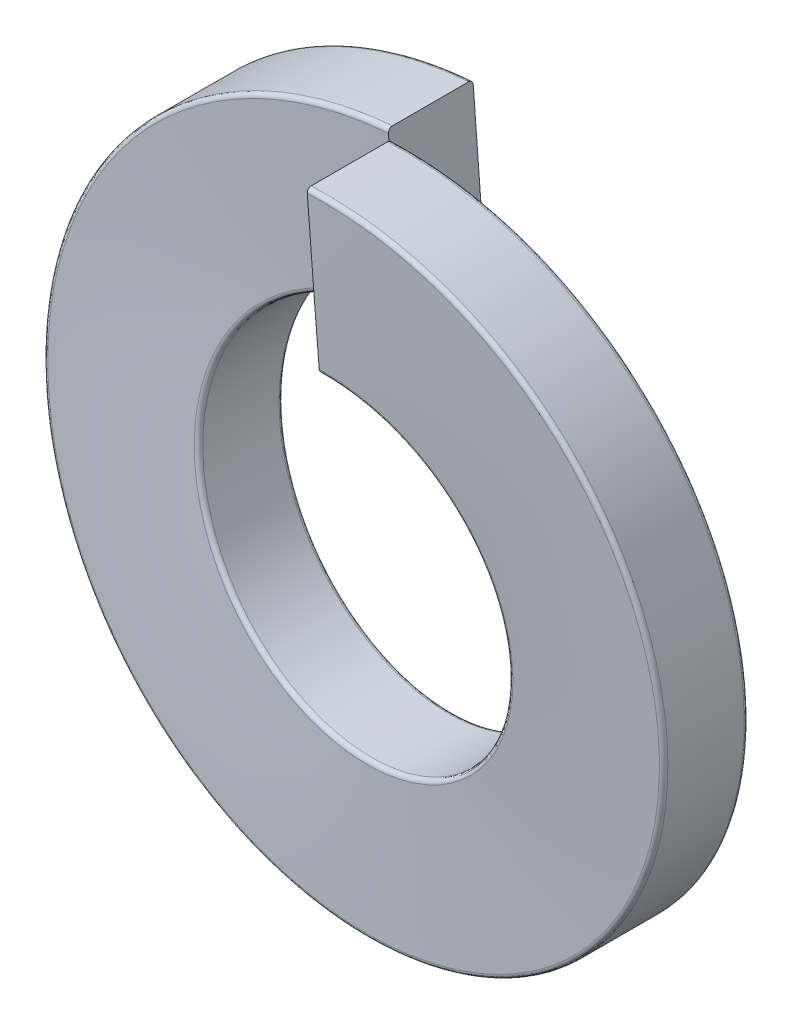
SolidWorks part; units mm, degrees
note: '?' marks a value the reader was unsure of.
material "AISI 316 Stainless Steel Sheet (SS)"
ref_plane "Front Plane" through (0, 0, 0) normal (0, 0, 1) x (1, 0, 0)
ref_plane "Top Plane" through (0, 0, 0) normal (0, 1, 0) x (1, 0, 0)
ref_plane "Right Plane" through (0, 0, 0) normal (1, 0, 0) x (0, 0, -1)
sketch "Sketch1" plane through (0, 0, 0) normal (0, 0, 1) x (1, 0, 0)
  circle A0 centre (0, 0) radius 3.302
  circle A1 centre (0, 0) radius 6.1849
  dimension "OD" = 12.3698
  dimension "ID" = 6.604
sketch "Sketch2" plane through (0, 0, 0) normal (1, 0, 0) x (0, 0, -1)
  line L0 (0, 0) -> (0, 6.1849) construction
  line L1 (0, 6.1849) -> (0, -6.1849) construction
  line L4 (0.1575, 6.1849) -> (1.7323, 6.1849)
  line L5 (1.7323, 6.1849) -> (1.7323, 3.302)
  line L6 (1.7323, 3.302) -> (0.1575, 3.302)
  line L7 (0.1575, 3.302) -> (0.1575, 6.1849)
  point P6 (0, 3.302)
  point P14 (0, -6.1849)
  dimension "Thickness" = 1.5748
  dimension "D1" = 0.1575
ref_plane "Plane1" through (0, 0, -1.7323) normal (0, 0, 1) x (1, 0, 0)
sketch "Sketch3" plane through (0, 0, -1.7323) normal (0, 0, 1) x (1, 0, 0)
  circle A0 centre (0, 0) radius 6.1849 construction
  circle A1 centre (0, 0) radius 6.1849
curve "Helix/Spiral1" pitch 1.7323 height 1.7323 turns 1
sketch "Sketch4" plane through (0, 0, 0) normal (1, 0, 0) x (0, 0, -1)
  line L0 (0.1575, 3.302) -> (0.1575, 6.1849) construction
  line L1 (1.7323, 3.302) -> (0.1575, 3.302) construction
  line L2 (1.7323, 6.1849) -> (1.7323, 3.302) construction
  line L3 (0.1575, 6.1849) -> (1.7323, 6.1849) construction
  line L4 (0.1575, 3.302) -> (0.1575, 6.1849)
  line L5 (1.7323, 3.302) -> (0.1575, 3.302)
  line L6 (1.7323, 6.1849) -> (1.7323, 3.302)
  line L7 (0.1575, 6.1849) -> (1.7323, 6.1849)
sweep "Sweep1" add profiles "Sketch4" path "Helix/Spiral1"
fillet "Fillet1" radius 0.0787 4 edges
sketch "Sketch5" plane through (0, 0, 0) normal (0, 0, 1) x (1, 0, 0)
  line L2 (0, 0) -> (-0.1079, 6.184) construction
  line L3 (0, 6.1849) -> (0.2167, 3.2949)
  line L4 (-0.2158, 6.1811) -> (0, 3.302)
  line L5 (-0.2158, 6.1811) -> (0, 0) construction
  line L6 (0, 0) -> (0, 6.1849) construction
  line L7 (0, 3.302) -> (0, 0)
  line L8 (0, 0) -> (0.2167, 0)
  line L9 (0.2167, 0) -> (0.2167, 3.2949)
  circle A0 centre (0, 0) radius 6.1849 construction
  arc A1 (-0.2158, 6.1811) -> (0, 6.1849) centre (0, 0) cw
  circle A2 centre (0, 0) radius 3.302 construction
  dimension "D1" = 2
extrude "Cut-Extrude1" cut sketch "Sketch5" against normal through all both and the other way through all
ref_axis "Center Axis" through (0, 0, 0) along (0, 0, 1)?
ref_plane "Contact Plane1" through (0, 0, 1.5745) normal (0, 0, 1) x (1, 0, 0)
ref_plane "Contact Plane2" through (0, 0, -1.7318) normal (0, 0, 1) x (1, 0, 0)
equation "\"D1@Sketch2\" = \"Thickness@Sketch2\" * 0.1"
equation "\"D4@Helix/Spiral1\" = \"Thickness@Sketch2\" + \"D1@Sketch2\""
equation "\"D1@Fillet1\"=\"D1@Sketch2\"*0.5"
